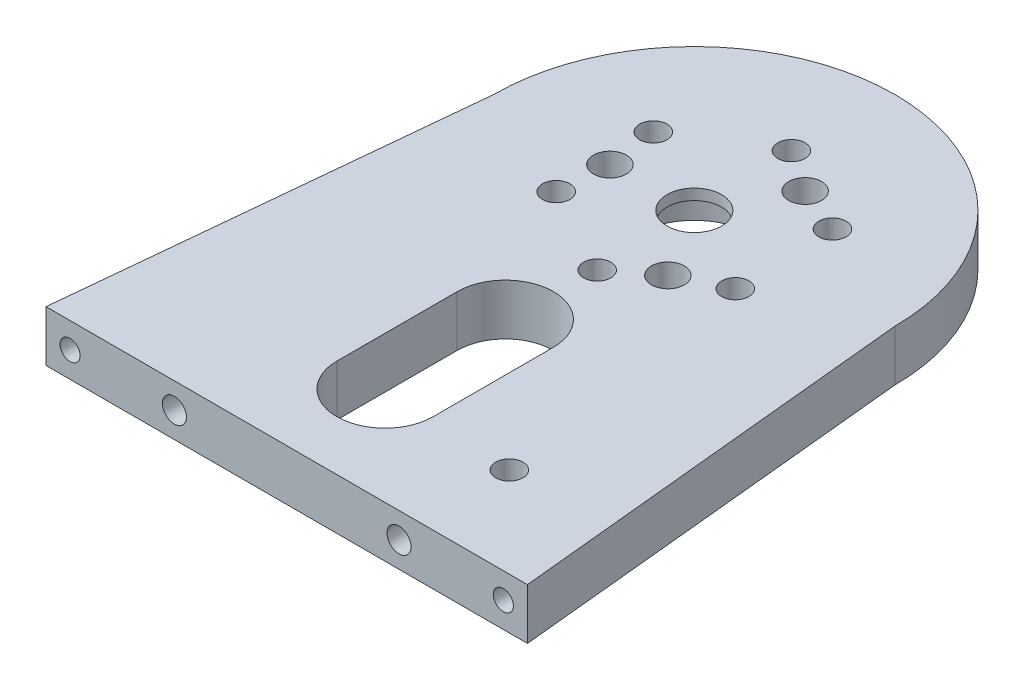
SolidWorks part; units mm, degrees
material "Aleación 6061"
ref_plane "Alzado" through (0, 0, 0) normal (0, 0, 1) x (1, 0, 0)
ref_plane "Planta" through (0, 0, 0) normal (0, 1, 0) x (1, 0, 0)
ref_plane "Vista lateral" through (0, 0, 0) normal (1, 0, 0) x (0, 0, -1)
ref_plane "Plano_zJ2" through (0, 0, 171.45) normal (0, 0, 1) x (1, 0, 0)
ref_plane "Plano_xJ3" through (152.4, 0, 0) normal (1, 0, 0) x (0, 0, -1)
ref_axis "Eje_J3" through (152.4, -33, 171.45) along (0, 1, 0)
ref_axis "Eje_J4" through (152.4, 0, 226.04) along (0, 0, -1)
sketch "Croquis12" plane through (0, 0, 0) normal (0, 1, 0) x (1, 0, 0)
  line L0 (127.4, -171.45) -> (177.4, -171.45)
  line L1 (177.4, -171.45) -> (182.4, -222.25)
  line L2 (182.4, -222.25) -> (122.4, -222.25)
  line L3 (122.4, -222.25) -> (127.4, -171.45)
  dimension "D1" = 127.4
  dimension "D2" = 171.45
  dimension "D3" = 177.4
  dimension "D4" = 171.45
  dimension "D5" = 182.4
  dimension "D6" = 222.25
  dimension "D7" = 122.4
  dimension "D8" = 222.25
extrude "Placa_antebrazo" add sketch "Croquis12" along normal blind 6.35 from offset 3.175 offset against normal yes
sketch "Croquis13" plane through (0, 0, 0) normal (0, 1, 0) x (1, 0, 0)
  circle A0 centre (152.4, -171.45) radius 25
  dimension "D1" = 50
  dimension "D2" = 152.4
  dimension "D3" = 171.45
extrude "Placa_antebrazo_redondeo" add sketch "Croquis13" along normal blind 6.35 from offset 3.175 offset against normal yes
sketch "Croquis14" plane through (0, 0, 0) normal (0, 1, 0) x (1, 0, 0)
  circle A0 centre (163.4163, -177.3569) radius 1.7
  circle A1 centre (152.7926, -183.9438) radius 1.7
  circle A2 centre (141.7763, -178.0369) radius 1.7
  circle A3 centre (141.3837, -165.5431) radius 1.7
  circle A4 centre (152.0074, -158.9562) radius 1.7
  circle A5 centre (163.0237, -164.8631) radius 1.7
  circle A6 centre (157.7749, -180.1189) radius 2.05
  circle A7 centre (142.205, -171.7704) radius 2.05
  circle A8 centre (157.22, -162.4607) radius 2.05
  circle A9 centre (152.4, -171.45) radius 3.4
  dimension "D1" = 3.4
  dimension "D2" = 3.4
  dimension "D3" = 3.4
  dimension "D4" = 3.4
  dimension "D5" = 3.4
  dimension "D6" = 3.4
  dimension "D7" = 4.1
  dimension "D8" = 4.1
  dimension "D9" = 4.1
  dimension "D10" = 6.8
  dimension "D11" = 163.4163
  dimension "D12" = 177.3569
  dimension "D13" = 152.7926
  dimension "D14" = 183.9438
  dimension "D15" = 141.7763
  dimension "D16" = 178.0369
  dimension "D17" = 141.3837
  dimension "D18" = 165.5431
  dimension "D19" = 152.0074
  dimension "D20" = 158.9562
  dimension "D21" = 163.0237
  dimension "D22" = 164.8631
  dimension "D23" = 157.7749
  dimension "D24" = 180.1189
  dimension "D25" = 142.205
  dimension "D26" = 171.7704
  dimension "D27" = 157.22
  dimension "D28" = 162.4607
  dimension "D29" = 152.4
  dimension "D30" = 171.45
extrude "Barrenos_J3" cut sketch "Croquis14" along normal blind 6.35 from offset 3.175 offset against normal yes
sketch "Croquis15" plane through (0, 0, 0) normal (0, 1, 0) x (1, 0, 0)
  circle A0 centre (163.4163, -177.3569) radius 3
  circle A1 centre (152.7926, -183.9438) radius 3
  circle A2 centre (141.7763, -178.0369) radius 3
  circle A3 centre (141.3837, -165.5431) radius 3
  circle A4 centre (152.0074, -158.9562) radius 3
  circle A5 centre (163.0237, -164.8631) radius 3
  dimension "D1" = 6
  dimension "D2" = 6
  dimension "D3" = 6
  dimension "D4" = 6
  dimension "D5" = 6
  dimension "D6" = 6
  dimension "D7" = 163.4163
  dimension "D8" = 177.3569
  dimension "D9" = 152.7926
  dimension "D10" = 183.9438
  dimension "D11" = 141.7763
  dimension "D12" = 178.0369
  dimension "D13" = 141.3837
  dimension "D14" = 165.5431
  dimension "D15" = 152.0074
  dimension "D16" = 158.9562
  dimension "D17" = 163.0237
  dimension "D18" = 164.8631
extrude "Refrentados_J3" cut sketch "Croquis15" along normal blind 3.2 from offset 3.175 offset against normal yes
sketch "Croquis16" plane through (0, 0, 0) normal (0, 1, 0) x (1, 0, 0)
  line L0 (158.4, -195) -> (158.4, -210)
  line L1 (146.4, -210) -> (146.4, -195)
  arc A0 (158.4, -210) -> (146.4, -210) centre (152.4, -210) cw
  arc A1 (146.4, -195) -> (158.4, -195) centre (152.4, -195) cw
  dimension "D1" = 6
  dimension "D2" = 6
  dimension "D3" = 158.4
  dimension "D4" = 195
  dimension "D5" = 158.4
  dimension "D6" = 210
  dimension "D7" = 146.4
  dimension "D8" = 210
  dimension "D9" = 146.4
  dimension "D10" = 195
extrude "Aligerado_paso_cable" cut sketch "Croquis16" along normal blind 6.35 from offset 3.175 offset against normal yes
sketch "Croquis17" plane through (0, 0, 0) normal (0, 0, 1) x (1, 0, 0)
  circle A0 centre (125.4, 0) radius 1.25
  circle A1 centre (179.4, 0) radius 1.25
  dimension "D1" = 2.5
  dimension "D2" = 2.5
  dimension "D3" = 125.4
  dimension "D4" = 179.4
extrude "Rosca_M3_canto" cut sketch "Croquis17" along normal blind 9 from offset 213.25
sketch "Croquis18" plane through (0, 0, 0) normal (0, 0, 1) x (1, 0, 0)
  circle A0 centre (138.4, 0) radius 1.5
  circle A1 centre (166.4, 0) radius 1.5
  dimension "D1" = 3
  dimension "D2" = 3
  dimension "D3" = 138.4
  dimension "D4" = 166.4
extrude "Pasadores_D3" cut sketch "Croquis18" along normal blind 7 from offset 215.25
sketch "Croquis19" plane through (0, 0, 0) normal (0, 1, 0) x (1, 0, 0)
  circle A0 centre (171.4, -211) radius 1.25
  circle A1 centre (166.4, -211) radius 1.25
  dimension "D1" = 2.5
  dimension "D2" = 2.5
  dimension "D3" = 171.4
  dimension "D4" = 211
  dimension "D5" = 166.4
  dimension "D6" = 211
sketch "Croquis20" plane through (0, 0, 0) normal (0, 1, 0) x (1, 0, 0)
  circle A0 centre (168.9, -211) radius 1.7
  dimension "D1" = 3.4
  dimension "D2" = 168.9
  dimension "D3" = 211
extrude "Paso_M3_bases_cincho" cut sketch "Croquis20" along normal blind 6.35 from offset 3.175 offset against normal yes
sketch "Croquis21" plane through (0, -3.175, 0) normal (0, -1, 0) x (1, 0, 0)
  circle A0 centre (152.4, 171.45) radius 7.45
  dimension "D1" = 14.9
extrude "Cortar-Extruir1" cut sketch "Croquis21" against normal blind 5
